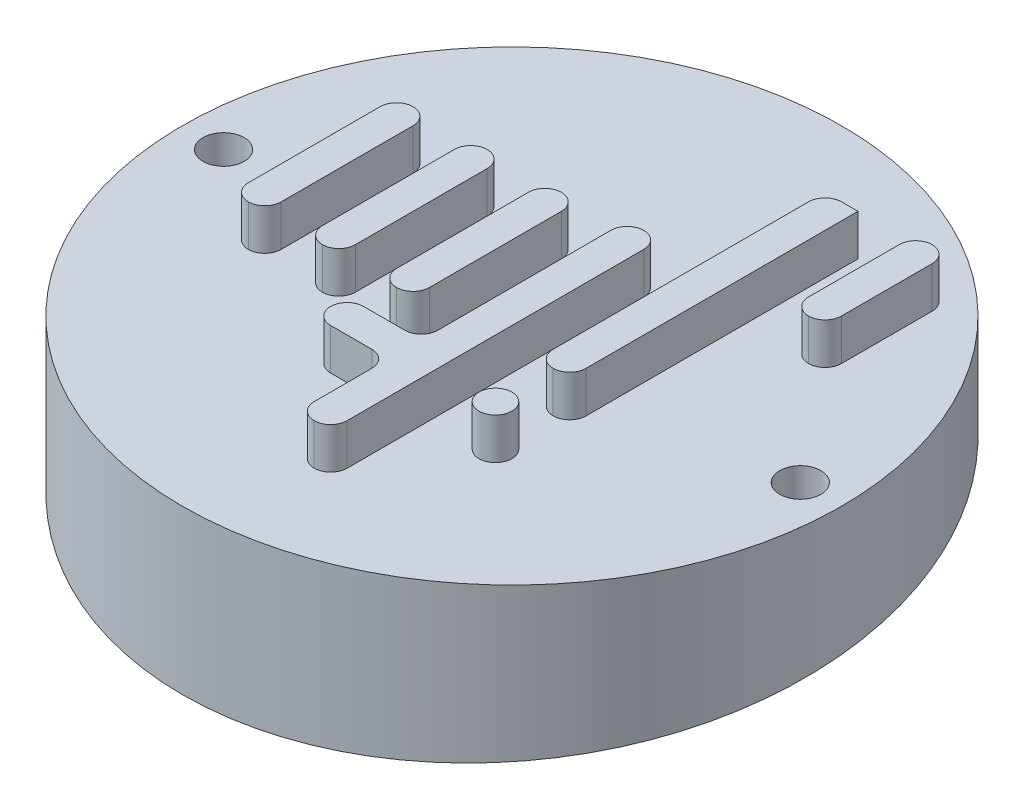
SolidWorks part; units mm, degrees
material "Brass"
ref_plane "Front Plane" through (0, 0, 0) normal (0, 0, 1) x (1, 0, 0)
ref_plane "Top Plane" through (0, 0, 0) normal (0, 1, 0) x (1, 0, 0)
ref_plane "Right Plane" through (0, 0, 0) normal (1, 0, 0) x (0, 0, -1)
sketch "Sketch1" plane through (0, 0, 0) normal (0, 1, 0) x (1, 0, 0)
  line L0 (0, -10) -> (-2, -10) construction
  line L1 (0, -20) -> (-2, -20)
  line L2 (0, -20) -> (0, 0)
  line L3 (0, 0) -> (-2, 0)
  line L4 (-2, -20) -> (-2, 0)
  line L5 (4.5, -10) -> (2.5, -10)
  line L6 (4.5, -10) -> (4.5, 7.5)
  line L7 (4.5, 7.5) -> (2.5, 7.5)
  line L8 (2.5, -10) -> (2.5, 7.5)
  line L9 (-4.5, -10.5) -> (-6.5, -10.5)
  line L10 (-4.5, -10.5) -> (-4.5, -0.5)
  line L11 (-4.5, -0.5) -> (-6.5, -0.5)
  line L12 (-6.5, -10.5) -> (-6.5, -0.5)
  line L13 (-9, -10.5) -> (-11, -10.5)
  line L14 (-9, -10.5) -> (-9, -0.5)
  line L15 (-9, -0.5) -> (-11, -0.5)
  line L16 (-11, -10.5) -> (-11, -0.5)
  line L17 (-13.5, -10.5) -> (-15.5, -10.5)
  line L18 (-13.5, -10.5) -> (-13.5, -0.5)
  line L19 (-13.5, -0.5) -> (-15.5, -0.5)
  line L20 (-15.5, -10.5) -> (-15.5, -0.5)
  line L21 (9.5, 0.5) -> (7.5, 0.5)
  line L22 (9.5, 0.5) -> (9.5, 8)
  line L23 (9.5, 8) -> (7.5, 8)
  line L24 (7.5, 0.5) -> (7.5, 8)
  line L25 (4.5, -10) -> (-11, -10) construction
  line L26 (3.5, -14.5) -> (-5.5, -14.5)
  line L27 (3.5, -12.5) -> (-5.5, -12.5)
  line L28 (9.5, -20) -> (-15.5, 8) construction
  line L29 (9.5, 8) -> (-15.5, 8) construction
  line L30 (9.5, 8) -> (9.5, -20) construction
  line L31 (9.5, -20) -> (-15.5, -20) construction
  line L32 (-15.5, 8) -> (-15.5, -20) construction
  circle A0 centre (3.5, -13.5) radius 1
  circle A1 centre (-5.5, -13.5) radius 1
  circle A2 centre (-3, -6) radius 20
  point P29 (3.5, -10)
  point P35 (-5.5, -10.5)
  dimension "D11" = 2
  dimension "D15" = 40
  dimension "D1" = 20
  dimension "D2" = 2
  dimension "D3" = 3
  dimension "D4" = 2.5
  dimension "D5" = 2.5
  dimension "D6" = 2.5
  dimension "D7" = 2.5
  dimension "D8" = 10
  dimension "D9" = 0.5
  dimension "D10" = 3.5
  dimension "D12" = 17.5
  dimension "D13" = 0.5
  dimension "D14" = 7.5
extrude "Boss-Extrude2" add sketch "Sketch1" along normal blind 2.5 contours L24 L21 L22 L23 | L8 L5 L6 L7 | L27 L2 L3 L4 | A0 | L2 L26 L4 L1 | L2 L27 L4 L26 | A1 L26 L4 L27 | A1 | L12 L9 L10 L11 | L16 L13 L14 L15 | L20 L17 L18 L19 region at (-1, 0, 17.25) region at (-1, 0, 13.5) region at (-3.3665, 0, 13.5) region at (-1, 0, 6.25) region at (3.5, 0, 13.5) region at (-5.5, 0, 13.5) region at (3.5, 0, 1.25) region at (-5.5, 0, 5.5) region at (-10, 0, 5.5) region at (-14.5, 0, 5.5) region at (8.5, 0, -4.25)
extrude "Boss-Extrude3" add sketch "Sketch1<6>" against normal blind 20 contours A2
sketch "Sketch1<6>" plane through (0, 0, 0) normal (0, 1, 0) x (1, 0, 0) same geometry as "Sketch1"
sketch "Sketch2" plane through (4.5, 0, 0) normal (1, 0, 0) x (0, 0, -1)
  line L0 (14, -5.6979) -> (-26, -9.9021)
  line L1 (14, -20) -> (14, 0) construction
  line L2 (-26, 0) -> (-26, -20) construction
  line L4 (14, 0) -> (-26, 0) construction
  line L5 (-26, 0) -> (14, 0) construction
  line L6 (-26, -9.9021) -> (-26, -20)
  line L7 (-26, -20) -> (14, -20)
  line L8 (14, -20) -> (14, -5.6979)
  point P12 (-6, 0)
  point P13 (-6, -7.8)
  dimension "D1" = 6
  dimension "D2" = 7.8
extrude "Cut-Extrude1" cut sketch "Sketch2" against normal through all both and the other way through all
fillet "Fillet1" radius 1 25 edges at (-13.5, 1.25, 10.5) (-13.5, 1.25, 0.5) (-9, 1.25, 0.5) (-9, 1.25, 10.5) (-4.5, 1.25, 0.5) (-4.5, 1.25, 10.5) (0, 1.25, 20) (0, 1.25, 0) (9.5, 1.25, -8) (9.5, 1.25, -0.5) (4.5, 1.25, 10) (-15.5, 1.25, 0.5) (-15.5, 1.25, 10.5) (-11, 1.25, 0.5) (-11, 1.25, 10.5) (-6.5, 1.25, 0.5) (-6.5, 1.25, 10.5) (7.5, 1.25, -0.5) (7.5, 1.25, -8) (2.5, 1.25, -7.5) (2.5, 1.25, 10) (-2, 1.25, 0) (-2, 1.25, 14.5) (-2, 1.25, 20) (-2, 1.25, 12.5)
sketch "Sketch3" plane through (0, 0, 0) normal (0, 1, 0) x (1, 0, 0)
  line L0 (17, -6) -> (-23, -6) construction
  circle A0 centre (-3, -6) radius 20 construction
  point P5 (14.5, -6)
  point P6 (-20.5, -6)
  point P7 (0, 0)
  dimension "D1" = 35
  dimension "D2" = 2.5
hole_wizard "M3x0.5 Tapped Hole1" positions "3DSketch1" profile "Sketch4" tap size "M3x0.5" standard "ANSI Metric"
sketch3d "3DSketch1"
  point P0 (14.5, 0, 6)
  point P3 (-20.5, 0, 6)
sketch "Sketch4" plane through (14.5, 0, 6) normal (1, 0, 0) x (0, 0, 1)
  line L0 (0, 0) -> (0, 3.4511)
  line L1 (0, 3.4511) -> (1.25, 2.7)
  line L2 (1.25, 2.7) -> (1.25, 0)
  line L5 (1.25, 0) -> (0, 0)
  line L10 (0, 3.4511) -> (-1.25, 2.7) construction
  line L11 (0, -6.35) -> (0, 107.95) construction
  dimension "Tap Drill Dia." = 2.5
  dimension "Tap Drill Depth" = 2.7
  dimension "Drill Angle" = 118
cosmetic thread "Hole Thread1" parameters "D1"=2.7, "D2"=3
cosmetic thread "Hole Thread2" parameters "D1"=2.7, "D2"=3
